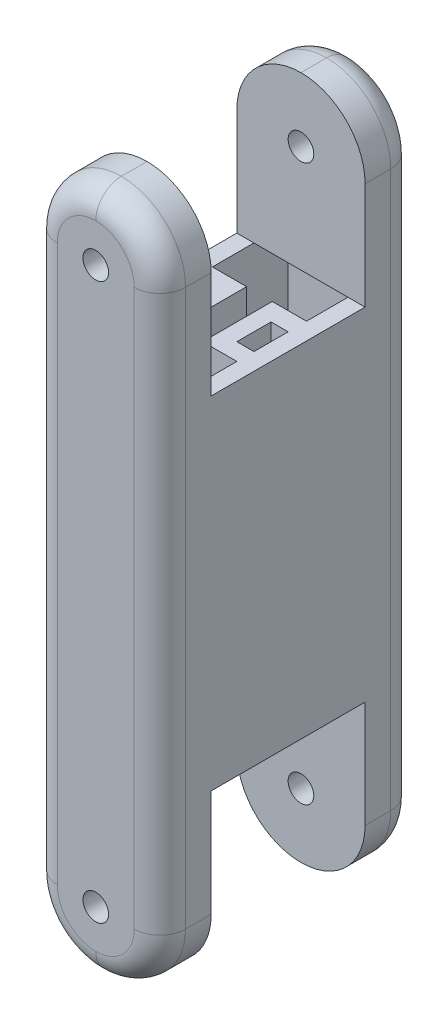
SolidWorks part; units mm, degrees
ref_plane "Front Plane" through (0, 0, 0) normal (0, 0, 1) x (1, 0, 0)
ref_plane "Top Plane" through (0, 0, 0) normal (0, 1, 0) x (1, 0, 0)
ref_plane "Right Plane" through (0, 0, 0) normal (1, 0, 0) x (0, 0, -1)
sketch "Sketch1" plane through (0, 0, 0) normal (0, 1, 0) x (1, 0, 0)
  line L0 (0, 0) -> (-10.7454, 0) construction
  line L1 (-7.5, -15) -> (7.5, -15)
  line L2 (-7.5, -15) -> (-7.5, 15)
  line L3 (-7.5, 15) -> (7.5, 15)
  line L4 (7.5, -15) -> (7.5, 15)
  line L5 (-7.5, -15) -> (7.5, 15) construction
  line L6 (-7.5, 15) -> (7.5, -15) construction
  line L7 (-5.5, -13) -> (5.5, -13)
  line L8 (-5.5, -13) -> (-5.5, -4.2085)
  line L9 (-5.5, 13) -> (5.5, 13)
  line L10 (5.5, -13) -> (5.5, -4)
  line L11 (-5.5, -13) -> (5.5, 13) construction
  line L12 (-5.5, 13) -> (5.5, -13) construction
  line L13 (-10.7454, 0) -> (11.7241, 0) construction
  line L14 (-5.5, 4.1445) -> (-1.5, 4.1445)
  line L15 (-1.5, 4.1445) -> (-1.5, -4.2085)
  line L16 (-1.5, -4.2085) -> (-5.5, -4.2085)
  line L17 (-5.5, 2) -> (-3.5, 2)
  line L18 (-3.5, 2) -> (-3.5, -2.4963)
  line L19 (-3.5, -2.4963) -> (-5.5, -2.4963)
  line L20 (5.5, 4.1445) -> (1.5, 4.1445)
  line L21 (1.5, 4.1445) -> (1.5, -4)
  line L22 (1.5, -4) -> (5.5, -4)
  line L23 (5.5, 2) -> (3.5, 2)
  line L24 (3.5, 2) -> (3.5, -2)
  line L25 (3.5, -2) -> (5.5, -2)
  line L26 (-5.5, 4.1445) -> (-5.5, 13)
  line L27 (5.5, 4.1445) -> (5.5, 13)
  line L28 (-5.5, 2) -> (-5.5, -2.4963)
  line L29 (5.5, 2) -> (5.5, -2)
  point P0 (0, 0)
  point P6 (0, 0)
  dimension "D1" = 2
  dimension "D2" = 2
  dimension "D3" = 2
  dimension "D4" = 2
  dimension "D5" = 2
  dimension "D6" = 2
  dimension "D7" = 2
  dimension "D8" = 2
  dimension "D9" = 2
  dimension "D10" = 2
  dimension "D11" = 15
  dimension "D12" = 30
extrude "Boss-Extrude1" add sketch "Sketch1" along normal blind 40 from offset 20 offset against normal yes
sketch "Sketch2" plane through (0, -20, 0) normal (0, -1, 0) x (1, 0, 0)
  line L0 (-7.5, -15) -> (-7.5, 15) construction
  line L1 (7.5, 15) -> (-7.5, 15)
  line L2 (7.5, 15) -> (7.5, 9)
  line L3 (7.5, 9) -> (-7.5, 9)
  line L4 (-7.5, 15) -> (-7.5, 9)
  line L6 (7.5, -15) -> (-7.5, -15)
  line L7 (7.5, -15) -> (7.5, -9)
  line L8 (7.5, -9) -> (-7.5, -9)
  line L9 (-7.5, -15) -> (-7.5, -9)
  dimension "D1" = 6
  dimension "D2" = 6
extrude "Boss-Extrude2" add sketch "Sketch2" along normal blind 20
fillet "Fillet1" radius 7.5 4 edges at (-7.5, -40, 12) (-7.5, -40, -12) (7.5, -40, -12) (7.5, -40, 12)
sketch "Sketch3" plane through (0, 0, 15) normal (0, 0, 1) x (1, 0, 0)
  circle A0 centre (0, -32.5) radius 1.5
  dimension "D1" = 3
extrude "Cut-Extrude1" cut sketch "Sketch3" against normal through all
mirror "Mirror1" about plane through (0, 0, 0) normal (0, 1, 0) of "Boss-Extrude2", "Fillet1", "Cut-Extrude1"
fillet "Fillet4" radius 3 12 edges at (-5.3033, 37.8033, 15) (5.3033, 37.8033, 15) (7.5, 0, 15) (5.3033, -37.8033, 15) (-5.3033, -37.8033, 15) (-5.3033, -37.8033, -15) (5.3033, -37.8033, -15) (7.5, 0, -15) (5.3033, 37.8033, -15) (-5.3033, 37.8033, -15) (-7.5, 0, -15) (-7.5, 0, 15)
